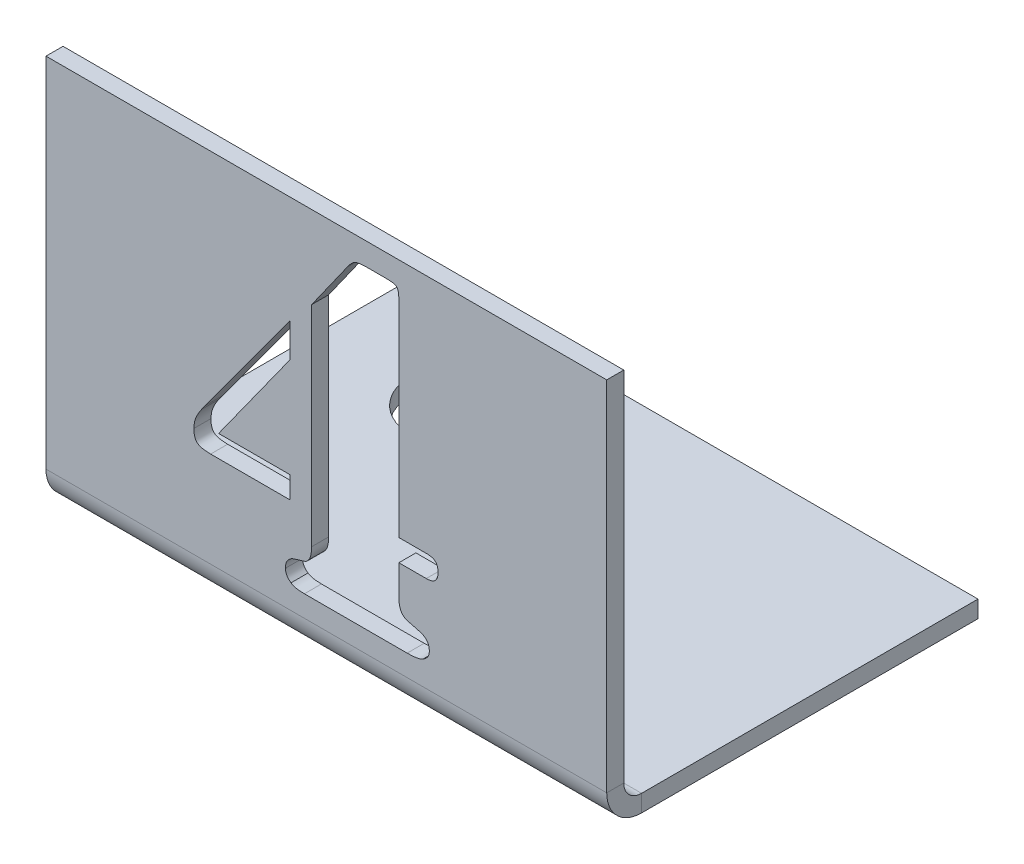
SolidWorks part; units mm, degrees
note: The reader was unsure of these and kept them because the rebuilt part matched: flange length of "Edge-Flange1".
material "16 Ga. SHEET METAL"
ref_plane "Front Plane" through (0, 0, 0) normal (0, 0, 1) x (1, 0, 0)
ref_plane "Top Plane" through (0, 0, 0) normal (0, 1, 0) x (1, 0, 0)
ref_plane "Right Plane" through (0, 0, 0) normal (1, 0, 0) x (0, 0, -1)
sketch "Sketch1" plane through (0, 0, 0) normal (0, 1, 0) x (1, 0, 0)
  line L1 (-25, 0) -> (25, 0)
  line L2 (-25, 0) -> (-25, 30)
  line L3 (-25, 30) -> (25, 30)
  line L4 (25, 0) -> (25, 30)
  dimension "D1" = 30
  dimension "D2" = 50
base flange "Base-Flange1" sketch "Sketch1" thickness 1.5189 reverse thickness direction yes parameters "D1"=1.5875
edge flange "Edge-Flange1" sketch "Sketch8" flange angle 90 flange length 35 flange position bend outside bend radius 1.5875 thickness 1.5189 relief rectangular parameters "D6"=10
sketch "Sketch8" plane through (0, 1.5189, 0) normal (0, 0, 1) x (1, 0, 0)
  line L0 (-25, 0) -> (25, 0) construction
  line L1 (-25, 0) -> (25, 0)
  line L2 (-25, 0) -> (-25, 33.4811)
  line L3 (-25, 33.4811) -> (25, 33.4811)
  line L4 (25, 33.4811) -> (25, 0)
bend "EdgeBend1" bend radius 1.5875 bend angle 90 parameters "D5"=1
hole_wizard "M8 Clearance Hole1" positions "Sketch9" profile "Sketch10" hole size "M8" standard "Peddi DIN" end condition through all
sketch "Sketch9" plane through (0, 1.5189, 0) normal (0, 1, 0) x (1, 0, 0)
  line L0 (25, -3.1064) -> (-25, -3.1064) construction
  line L1 (-25, 30) -> (-25, 0) construction
  point P0 (-13, 21.8936)
  dimension "D1" = 25
  dimension "D2" = 12
sketch "Sketch10" plane through (-13, 1.5189, -21.8936) normal (1, 0, 0) x (0, 0, 1)
  line L0 (0, 0) -> (0, 1.5189)
  line L1 (0, 1.5189) -> (4.5, 1.5189)
  line L2 (4.5, 1.5189) -> (4.5, 0)
  line L5 (4.5, 0) -> (0, 0)
  line L11 (0, -6.35) -> (0, 107.95) construction
  dimension "Thru Hole Dia." = 9
  dimension "Thru Hole Depth" = 1.5189
sketch "Sketch11" plane through (0, 0, 3.1064) normal (0, 0, 1) x (1, 0, 0)
  line L0 (-25, 0) -> (25, 0) construction
  text T0 "4" font "Stencil" height 28
  dimension "D1" = 5
extrude "Cut-Extrude1" cut sketch "Sketch11" against normal through all
other "Freeze***"
sketch "Bend-Lines1" [suppressed] plane through (0, 0, 0) normal (0, 1, 0) x (1, 0, 0)
sketch "Bounding-Box1" [suppressed] plane through (0, 0, 0) normal (0, 1, 0) x (1, 0, 0)
sheet metal parameters "Sheet-Metal1" thickness 1.5189 parameters "D1"=1.5875
flat pattern "Flat-Pattern1" [suppressed]
sketch "Bend-Lines2" plane through (0, 0, 0) normal (0, 1, 0) x (1, 0, 0)
sketch "Bounding-Box2" [suppressed] plane through (0, 0, 0) normal (0, 1, 0) x (1, 0, 0)
sheet metal parameters "Sheet-Metal2" thickness 1.5189 parameters "D1"=1.5875
flat pattern "Flat-Pattern1" [suppressed]
sketch "Bend-Lines2" plane through (0, 0, 0) normal (0, 1, 0) x (1, 0, 0)
sketch "Bounding-Box2" [suppressed] plane through (0, 0, 0) normal (0, 1, 0) x (1, 0, 0)
bend of the flat pattern "Flatten-<EdgeBend1>1"
sheet metal parameters "Sheet-Metal3" thickness 1.5189 parameters "D1"=1.5875
flat pattern "Flat-Pattern1" [suppressed]
sketch "Bend-Lines2" plane through (0, 0, 0) normal (0, 1, 0) x (1, 0, 0)
sketch "Bounding-Box2" [suppressed] plane through (0, 0, 0) normal (0, 1, 0) x (1, 0, 0)
bend of the flat pattern "Flatten-<EdgeBend1>1"
sheet metal parameters "Sheet-Metal4" thickness 1.5189 parameters "D1"=1.5875
flat pattern "Flat-Pattern1"
sketch "Bend-Lines2" plane through (0, 0, 0) normal (0, -1, 0) x (-1, 0, 0)
  line L0 (-25, -1.724) -> (25, -1.724) construction
  line L1 (-25, -1.724) -> (25, -1.724) construction
sketch3d "Bounding-Box2" [suppressed]
  line L0 (25, -35.3416, 0) -> (25, 30, 0) construction
  line L1 (-25, -35.3416, 0) -> (-25, 30, 0) construction
  line L2 (25, -35.3416, 0) -> (-25, -35.3416, 0) construction
  line L3 (25, 30, 0) -> (-25, 30, 0) construction
bend of the flat pattern "Flatten-<EdgeBend1>1"
